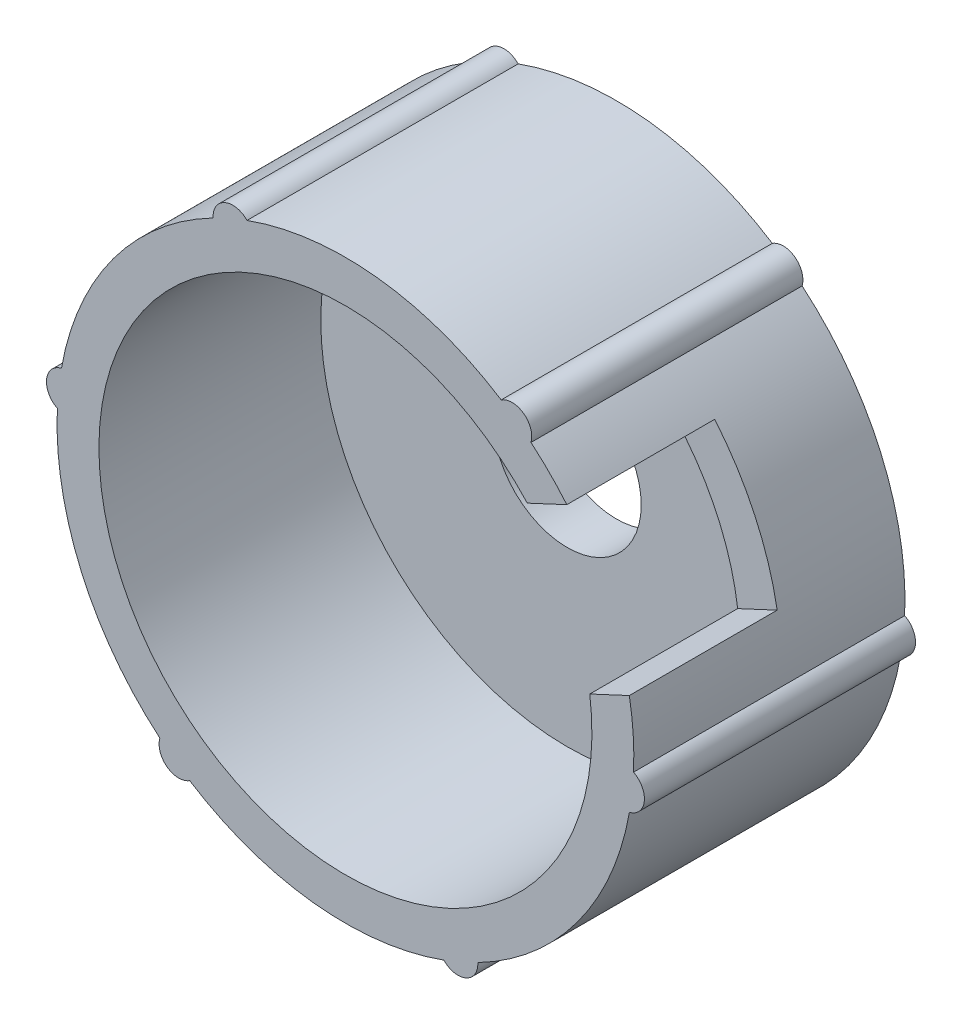
SolidWorks part; units mm, degrees
note: '?' marks a value the reader was unsure of. The reader was unsure of these and kept them because the rebuilt part matched: shared geometry of "Skizze2<4>".
ref_plane "Ebene vorne" through (0, 0, 0) normal (0, 0, 1) x (1, 0, 0)
ref_plane "Ebene oben" through (0, 0, 0) normal (0, 1, 0) x (1, 0, 0)
ref_plane "Ebene rechts" through (0, 0, 0) normal (1, 0, 0) x (0, 0, -1)
ref_plane "Ebene1" through (0, 0, 13.4) normal (0, 0, 1) x (1, 0, 0)
ref_plane "Ebene2" through (0, 0, 7.9) normal (0, 0, 1) x (1, 0, 0)
sketch "Skizze2" plane through (0, 0, 7.9) normal (0, 0, 1) x (1, 0, 0)
  circle A0 centre (94, 7) radius 5.85
  circle A1 centre (94, 7) radius 5
  dimension "D1" = 10
  dimension "D2" = 11.7
  dimension "D3" = 94
  dimension "D4" = 7
extrude "Aufsatz-Linear austragen1" add sketch "Skizze2" along normal blind 1 contours A1
extrude "Aufsatz-Linear austragen2" add sketch "Skizze2<4>" along normal up to surface (5.5 mm away) up to plane "Ebene1"
sketch "Skizze2<4>" plane through (0, 0, 7.9) normal (0, 0, 1) x (1, 0, 0) same geometry as "Skizze2"
ref_axis "Achse1" through (94, 7, 13.4) along (0, 0, -1)?
sketch "Skizze3" plane through (0, 0, 7.9) normal (0, 0, 1) x (1, 0, 0)
  line L0 (94, 7) -> (91.7148, 12.2219) construction
  circle A0 centre (91.7148, 12.2219) radius 0.4
  circle A1 centre (94, 7) radius 5.85 construction
  dimension "D1" = 0.8
  dimension "D2" = 5.7
extrude "Aufsatz-Linear austragen3" add sketch "Skizze3" along normal up to surface (5.5 mm away) up to plane "Ebene1"
pattern_circular "Kreismuster1" count 6 every 60 about axis through (94, 7, 0) along (0, 0, 1) of "Aufsatz-Linear austragen3"
sketch "Skizze4" plane through (0, 0, 13.4) normal (0, 0, 1) x (1, 0, 0)
  line L0 (93.3661, 8.3595) -> (100.2908, 11.5885)
  line L1 (100.2908, 11.5885) -> (101.5586, 8.8696)
  line L2 (101.5586, 8.8696) -> (94.6339, 5.6405)
  line L3 (94.6339, 5.6405) -> (93.3661, 8.3595)
  line L4 (94, 7) -> (100.9247, 10.229) construction
  line L5 (84.8529, 15.0865) -> (84.8529, -2.1279) construction
  circle A0 centre (94, 7) radius 5 construction
  dimension "D1" = 3
  dimension "D2" = 65
extrude "Schnitt-Linear austragen1" cut sketch "Skizze4" against normal blind 3
sketch "Skizze5" plane through (0, 0, 7.9) normal (0, 0, 1) x (1, 0, 0)
  circle A0 centre (94, 7) radius 1.5
  dimension "D1" = 3
extrude "Schnitt-Linear austragen2" cut sketch "Skizze5" along normal through all
other "Körper speichern1"
